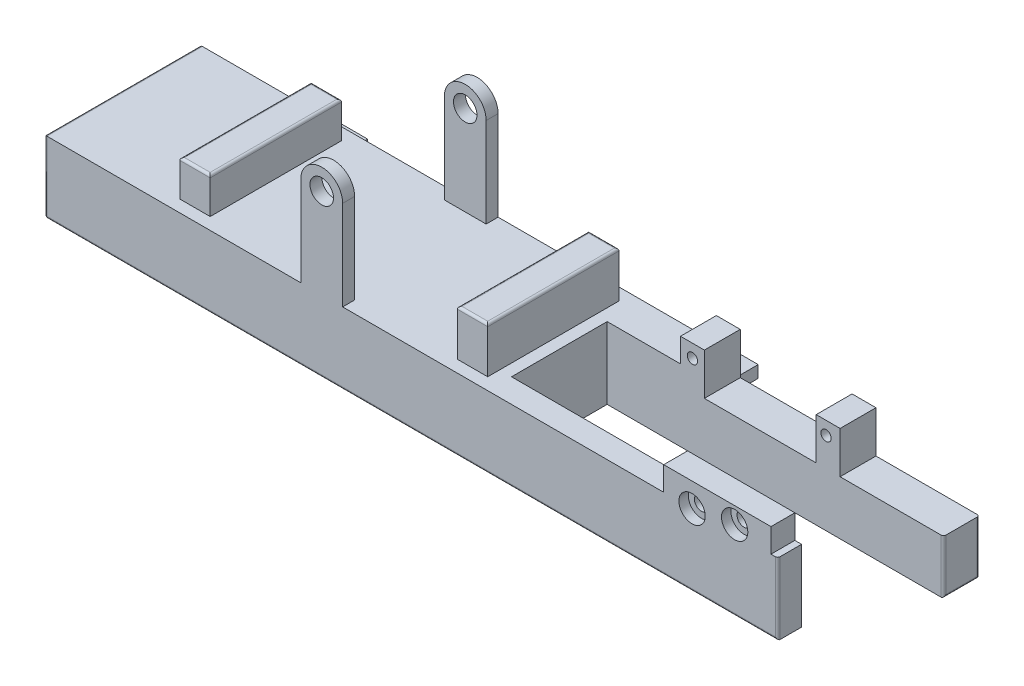
SolidWorks part; units mm, degrees
other "Markup1"
sketch "Sketch17" plane through (106.68, 38.735, 16.51) normal (0.2565, 0.8765, 0.4073) x (0.8462, 0, -0.5329)
ref_plane "Front" through (0, 0, 0) normal (0, 0, 1) x (1, 0, 0)
ref_plane "Top" through (0, 0, 0) normal (0, 1, 0) x (1, 0, 0)
ref_plane "Right" through (0, 0, 0) normal (1, 0, 0) x (0, 0, -1)
sketch "Sketch1" plane through (0, 0, 0) normal (0, 1, 0) x (1, 0, 0)
  line L0 (-58.8676, 16.51) -> (-58.8676, -16.51)
  line L1 (-106.68, 16.51) -> (106.68, 16.51)
  line L2 (-106.68, 16.51) -> (-106.68, -16.51)
  line L3 (-106.68, -16.51) -> (106.68, -16.51)
  line L4 (106.68, 16.51) -> (106.68, -16.51)
  line L5 (-106.68, 16.51) -> (106.68, -16.51) construction
  line L6 (-106.68, -16.51) -> (106.68, 16.51) construction
  line L7 (106.68, -16.51) -> (55.88, -16.51)
  line L8 (106.68, -16.51) -> (106.68, 8.89)
  line L9 (106.68, 8.89) -> (55.88, 8.89)
  line L10 (55.88, -16.51) -> (55.88, 8.89)
  line L11 (0, -55) -> (0, 55) construction
  line L12 (36.4884, 16.51) -> (46.4884, 16.51)
  line L13 (36.4884, 16.51) -> (36.4884, 29.718)
  line L14 (36.4884, 29.718) -> (46.4884, 29.718)
  line L15 (46.4884, 16.51) -> (46.4884, 29.718)
  line L16 (-36.4884, 29.718) -> (-46.4884, 29.718)
  line L17 (-46.4884, 16.51) -> (-46.4884, 29.718)
  line L18 (-36.4884, 16.51) -> (-46.4884, 16.51)
  line L19 (-36.4884, 16.51) -> (-36.4884, 29.718)
  line L21 (55.88, -16.51) -> (96.8527, -16.51)
  line L22 (55.88, -16.51) -> (55.88, -11.43)
  line L23 (55.88, -11.43) -> (96.8527, -11.43)
  line L24 (96.8527, -16.51) -> (96.8527, -11.43)
  circle A0 centre (-41.4884, 20.01) radius 2
  circle A1 centre (41.4884, 20.01) radius 2
  point P0 (0, 0)
  dimension "D7" = 4
  dimension "D1" = 213.36
  dimension "D2" = 33.02
  dimension "D3" = 25.4
  dimension "D4" = 50.8
  dimension "D5" = 10
  dimension "D6" = 13.208
  dimension "D8" = 5.08
extrude "Boss-Extrude1" add sketch "Sketch1" along normal blind 15.24 contours L3 L10 L9 L4 L1 L0 | L3 L24 L23 L10 region at (6.1788, 0, -1.1772) region at (76.3663, 0, 13.97)
sketch "Sketch3" plane through (0, 0, 16.51) normal (0, 0, 1) x (1, 0, 0)
  line L0 (4.445, 15.24) -> (-4.445, 15.24)
  line L1 (-58.8676, 15.24) -> (96.8527, 15.24) construction
  line L2 (-4.445, 15.24) -> (-4.445, 34.29)
  line L3 (4.445, 15.24) -> (4.445, 34.29)
  line L4 (0, -55) -> (0, 55) construction
  arc A0 (-4.445, 34.29) -> (4.445, 34.29) centre (0, 34.29) cw
  circle A1 centre (0, 34.29) radius 2.5
  point P8 (0, 15.24)
  dimension "D2" = 5
  dimension "D1" = 8.89
  dimension "D3" = 19.05
extrude "Boss-Extrude2" add sketch "Sketch3" against normal blind 2.54
mirror "Mirror1" about plane through (0, 0, 0) normal (0, 0, 1) of "Boss-Extrude2"
sketch "Sketch4" plane through (0, 15.24, 0) normal (0, 1, 0) x (1, 0, 0)
  line L0 (-55, 0) -> (55, 0) construction
  line L1 (26.2471, 13.9568) -> (32.7047, 13.9568)
  line L2 (26.2471, 13.9568) -> (26.2471, -13.9568)
  line L3 (26.2471, -13.9568) -> (32.7047, -13.9568)
  line L4 (32.7047, 13.9568) -> (32.7047, -13.9568)
  line L5 (0, -55) -> (0, 55) construction
  line L6 (-26.2471, -13.9568) -> (-32.7047, -13.9568)
  line L7 (-32.7047, 13.9568) -> (-32.7047, -13.9568)
  line L8 (-26.2471, 13.9568) -> (-32.7047, 13.9568)
  line L9 (-26.2471, 13.9568) -> (-26.2471, -13.9568)
  point P4 (26.2471, 0)
extrude "Boss-Extrude3" add sketch "Sketch4" along normal blind 7.62
sketch "Sketch11" plane through (0, 22.86, 0) normal (0, 1, 0) x (1, 0, 0)
  line L4 (-32.7047, -13.9568) -> (-26.2471, -13.9568)
  line L5 (-32.7047, 13.9568) -> (-32.7047, -13.9568)
  line L6 (-26.2471, 13.9568) -> (-32.7047, 13.9568)
  line L7 (-26.2471, -13.9568) -> (-26.2471, 13.9568)
  line L8 (-32.7047, -13.9568) -> (-26.2471, -13.9568)
  line L9 (-32.7047, 13.9568) -> (-32.7047, -13.9568)
  line L10 (-26.2471, 13.9568) -> (-32.7047, 13.9568)
  line L11 (-26.2471, -13.9568) -> (-26.2471, 13.9568)
  line L12 (32.7047, 13.9568) -> (26.2471, 13.9568)
  line L13 (32.7047, -13.9568) -> (32.7047, 13.9568)
  line L14 (26.2471, -13.9568) -> (32.7047, -13.9568)
  line L15 (26.2471, 13.9568) -> (26.2471, -13.9568)
  line L16 (32.7047, 13.9568) -> (26.2471, 13.9568)
  line L17 (32.7047, -13.9568) -> (32.7047, 13.9568)
  line L18 (26.2471, -13.9568) -> (32.7047, -13.9568)
  line L19 (26.2471, 13.9568) -> (26.2471, -13.9568)
  dimension "D1" = 0
  dimension "D2" = 0
extrude "Boss-Extrude6" add sketch "Sketch11" along normal blind 2.0955 contours L16 L19 L18 L17
sketch "Sketch6" plane through (0, 22.86, 0) normal (0, 1, 0) x (1, 0, 0)
  line L0 (-21.3042, 0) -> (21.3042, 0) construction
  line L1 (0, -18.161) -> (0, 18.161) construction
  line L4 (-26.2471, -13.9568) -> (-26.2471, 13.9568)
  line L5 (-26.2471, 13.9568) -> (-32.7047, 13.9568)
  line L6 (-32.7047, 13.9568) -> (-32.7047, -13.9568)
  line L7 (-32.7047, -13.9568) -> (-26.2471, -13.9568)
  line L8 (-26.2471, -13.9568) -> (-26.2471, 13.9568)
  line L9 (-26.2471, 13.9568) -> (-32.7047, 13.9568)
  line L10 (-32.7047, 13.9568) -> (-32.7047, -13.9568)
  line L11 (-32.7047, -13.9568) -> (-26.2471, -13.9568)
  circle A0 centre (-29.5986, 8.5505) radius 2.15
  circle A1 centre (-29.5986, -8.5505) radius 2.15
  circle A2 centre (29.5986, -8.5505) radius 2.15
  circle A3 centre (29.5986, 8.5505) radius 2.15
  dimension "D3" = 4.3
  dimension "D1" = 0
extrude "Cut-Extrude1" cut sketch "Sketch6" against normal blind 3.332 and the other way through all contours A3 | A2 | A1 | A0 | A0 | A1 region at (-29.5986, 22.86, -8.5505) region at (-29.5986, 22.86, 8.5505) region at (29.5986, 22.86, 8.5505) region at (29.5986, 22.86, -8.5505)
fillet "Fillet1" radius 0.508 18 edges at (-58.8676, 15.24, 0) (-58.8676, 0, 0) (106.68, 0, -12.7) (106.68, 7.62, -8.89) (106.68, 7.62, -16.51) (-58.8676, 7.62, -16.51) (-58.8676, 7.62, 16.51) (18.9925, 0, 16.51) (-29.4759, 22.86, 13.9568) (-32.7047, 22.86, 0) (-29.4759, 22.86, -13.9568) (-26.2471, 22.86, 0) (29.4759, 24.9555, 13.9568) (26.2471, 24.9555, 0) (29.4759, 24.9555, -13.9568) (32.7047, 24.9555, 0) (106.68, 15.24, -12.7) (96.8527, 7.62, 16.51)
sketch "Sketch8" plane through (0, 15.24, 0) normal (0, 1, 0) x (1, 0, 0)
  line L1 (58.1514, 8.382) -> (58.1514, -16.002)
  line L3 (56.8238, 8.89) -> (35.2338, 8.89)
  line L4 (56.8238, 8.89) -> (56.8238, -11.43)
  line L5 (56.8238, -11.43) -> (35.2338, -11.43)
  line L6 (35.2338, 8.89) -> (35.2338, -11.43)
  line M44 (55.88, -11.43) -> (55.88, 8.89)
  line M46 (96.8527, -11.43) -> (55.88, -11.43)
  dimension "D1" = 20.32
  dimension "D3" = 21.59
extrude "Cut-Extrude2" cut sketch "Sketch8" against normal through all contours L3 L6 L5 L4 M46 M44 region at (45.5569, 15.24, 1.27)
extrude "Boss-Extrude5" add sketch "Sketch1<3>" along normal blind 2.54 contours L1 L15 L14 L13 | L1 L19 L16 L17 region at (-41.4884, 0, -23.4404) region at (41.4884, 0, -23.4404)
sketch "Sketch1<3>" plane through (0, 0, 0) normal (0, 1, 0) x (1, 0, 0) same geometry as "Sketch1"
sketch "Sketch14" plane through (0, 0, -8.89) normal (0, 0, 1) x (1, 0, 0)
  line L0 (106.172, 15.24) -> (35.2338, 15.24) construction
  line L2 (106.68, 15.24) -> (106.68, 11.43)
  line L3 (106.68, 11.43) -> (55.88, 11.43)
  line L4 (55.88, 15.24) -> (55.88, 11.43)
  line L5 (106.68, 14.732) -> (106.68, 0.508) construction
  line L6 (55.88, 15.24) -> (106.68, 15.24)
  dimension "D1" = 3.81
  dimension "D4" = 50.8
extrude "Cut-Extrude5" cut sketch "Sketch14" against normal through all and the other way blind 9.2075
sketch "Sketch15" plane through (0, 0, -8.89) normal (0, 0, 1) x (1, 0, 0)
  line L0 (55.88, 15.24) -> (35.2338, 15.24) construction
  line L1 (50.8, 15.24) -> (55.88, 15.24)
  line L2 (50.8, 15.24) -> (50.8, 20.32)
  line L3 (50.8, 20.32) -> (55.88, 20.32)
  line L4 (55.88, 15.24) -> (55.88, 20.32)
  line L5 (106.172, 11.43) -> (55.88, 11.43) construction
  line L6 (79.629, 11.43) -> (84.709, 11.43)
  line L7 (79.629, 11.43) -> (79.629, 20.32)
  line L8 (79.629, 20.32) -> (84.709, 20.32)
  line L9 (84.709, 11.43) -> (84.709, 20.32)
  line L11 (55.88, 11.43) -> (55.88, 15.24) construction
  dimension "D1" = 5.08
  dimension "D2" = 23.749
  dimension "D3" = 5.08
  dimension "D4" = 5.08
extrude "Boss-Extrude7" add sketch "Sketch15" against normal up to vertex (7.62 mm away) up to point (55.88, 15.24, -16.51)
sketch "Sketch16" plane through (0, 0, -8.89) normal (0, 0, 1) x (1, 0, 0)
  line L0 (55.88, 11.43) -> (55.88, 20.32) construction
  line L1 (106.172, 11.43) -> (84.709, 11.43) construction
  circle A0 centre (53.34, 17.526) radius 1.0922
  circle A1 centre (81.7245, 17.526) radius 1.0922
  dimension "D1" = 2.1844
  dimension "D2" = 2.54
  dimension "D3" = 6.096
  dimension "D4" = 28.3845
extrude "Cut-Extrude6" cut sketch "Sketch16" against normal up to next
sketch "Sketch18" plane through (0, 15.24, 0) normal (0, 1, 0) x (1, 0, 0)
  line L0 (35.2338, -11.43) -> (96.8527, -11.43) construction
  line L1 (95.4237, -11.43) -> (72.6409, -11.43)
  line L2 (95.4237, -11.43) -> (95.4237, -16.51)
  line L3 (95.4237, -16.51) -> (72.6409, -16.51)
  line L4 (72.6409, -11.43) -> (72.6409, -16.51)
  line L5 (4.445, -16.51) -> (96.3447, -16.51) construction
extrude "Boss-Extrude8" add sketch "Sketch18" along normal blind 5.08
sketch "Sketch9" plane through (0, 0, 11.43) normal (0, 0, -1) x (-1, 0, 0)
  line L0 (-87.7134, 16.8367) -> (-78.6583, 15.24) construction
  line L2 (18.161, 0) -> (-18.161, 0) construction
  circle A0 centre (-87.7134, 16.8367) radius 1.4986
  circle A1 centre (-78.6583, 15.24) radius 1.4986
  dimension "D1" = 2.9972
  dimension "D4" = 15.24
  dimension "D2" = 9.1948
  dimension "D3" = 10
extrude "Cut-Extrude3" cut sketch "Sketch9" along normal blind 12.7 and the other way blind 12.7
sketch "Sketch10" plane through (0, 0, 16.51) normal (0, 0, 1) x (1, 0, 0)
  circle A0 centre (78.6583, 15.24) radius 2.794
  circle A1 centre (87.7134, 16.8367) radius 2.794
  circle M2 centre (87.7134, 16.8367) radius 1.4986
  circle M3 centre (78.6583, 15.24) radius 1.4986
  dimension "D1" = 5.588
extrude "Cut-Extrude4" cut sketch "Sketch10" against normal blind 2 contours A0 M3 | A1 M2 region at (75.9434, 15.24, 16.51) region at (84.9985, 16.8367, 16.51)
sketch "Sketch20" plane through (0, 22.86, 0) normal (0, 1, 0) x (1, 0, 0)
  circle A0 centre (29.5986, 8.5505) radius 2.15 construction
  circle A1 centre (29.5986, -8.5505) radius 2.15 construction
  circle A2 centre (-29.5986, -8.5505) radius 2.15 construction
  circle A3 centre (-29.5986, 8.5505) radius 2.15 construction
  circle A4 centre (29.5986, 8.5505) radius 2.15
  circle A5 centre (29.5986, -8.5505) radius 2.15
  circle A6 centre (-29.5986, -8.5505) radius 2.15
  circle A7 centre (-29.5986, 8.5505) radius 2.15
  circle M8 centre (-29.5986, -8.5505) radius 2.15
  circle M9 centre (-29.5986, 8.5505) radius 2.15
extrude "Boss-Extrude9" add sketch "Sketch20" against normal blind 1 contours M8 | M9 region at (-29.5986, 22.86, 8.5505) region at (-29.5986, 22.86, -8.5505)
sketch "Sketch21" plane through (0, 24.9555, 0) normal (0, 1, 0) x (1, 0, 0)
  circle A0 centre (29.5986, -8.5505) radius 2.15 construction
  circle A1 centre (29.5986, 8.5505) radius 2.15 construction
  circle A2 centre (29.5986, -8.5505) radius 2.15
  circle A3 centre (29.5986, 8.5505) radius 2.15
extrude "Boss-Extrude10" add sketch "Sketch21" against normal blind 1
